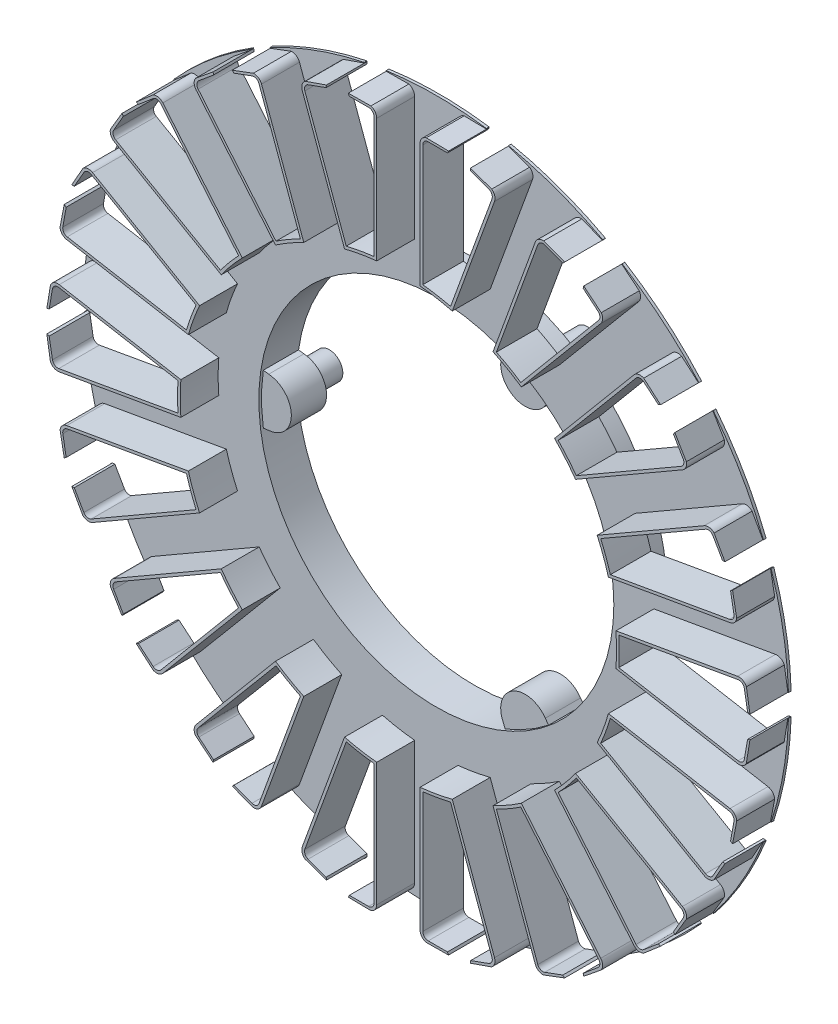
SolidWorks part; units mm, degrees
ref_plane "Front Plane" through (0, 0, 0) normal (0, 0, 1) x (1, 0, 0)
ref_plane "Top Plane" through (0, 0, 0) normal (0, 1, 0) x (1, 0, 0)
ref_plane "Right Plane" through (0, 0, 0) normal (1, 0, 0) x (0, 0, -1)
sketch "Sketch1" plane through (0, 0, 0) normal (0, 0, 1) x (1, 0, 0)
  line L0 (0, 0) -> (0, 65) construction
  line L1 (4.5, 40.5008) -> (4.5, 64.844) construction
  line L2 (-4.5, 40.5008) -> (-4.5, 62.8398)
  line L3 (9.25, 64.2333) -> (9.25, 64.3385)
  line L4 (9.05, 63.8336) -> (9.25, 64.2333)
  line L5 (-5.5018, 63.8398) -> (-9.05, 63.8336)
  line L6 (-9.25, 64.2333) -> (-9.25, 64.3385)
  line L7 (5.5018, 63.8398) -> (9.05, 63.8336)
  line L8 (-4.5, 0) -> (-4.5, 65) construction
  line L9 (-9.05, 63.8336) -> (-9.25, 64.2333)
  line L10 (4.5, 62.8398) -> (4.5, 40.5008)
  line L11 (4.5, 0) -> (4.5, 65) construction
  line L12 (25.7211, 57.5111) -> (18.0807, 36.5192)
  line L13 (13.3282, 63.0793) -> (13.2769, 63.5232)
  line L14 (13.2769, 63.5232) -> (13.3129, 63.6221)
  line L15 (16.6646, 61.8715) -> (13.3282, 63.0793)
  line L16 (27.0045, 58.1081) -> (30.3366, 56.8887)
  line L17 (30.6612, 57.1959) -> (30.6972, 57.2947)
  line L18 (30.3366, 56.8887) -> (30.6612, 57.1959)
  line L19 (9.6235, 39.5974) -> (17.2639, 60.5892)
  line L20 (43.8399, 45.2456) -> (29.4806, 28.1328)
  line L21 (34.0988, 54.7166) -> (34.2024, 55.1513)
  line L22 (34.2024, 55.1513) -> (34.2701, 55.2319)
  line L23 (36.8209, 52.4406) -> (34.0988, 54.7166)
  line L24 (45.25, 45.3677) -> (47.9642, 43.0822)
  line L25 (48.3743, 43.2598) -> (48.4419, 43.3403)
  line L26 (47.9642, 43.0822) -> (48.3743, 43.2598)
  line L27 (22.5862, 33.9179) -> (36.9455, 51.0307)
  line L28 (56.6709, 27.5228) -> (37.3247, 16.3533)
  line L29 (50.7565, 39.7543) -> (51.0027, 40.1274)
  line L30 (51.0027, 40.1274) -> (51.0937, 40.18)
  line L31 (52.5361, 36.6846) -> (50.7565, 39.7543)
  line L32 (58.0378, 27.1553) -> (59.8065, 24.0793)
  line L33 (60.2527, 24.1059) -> (60.3437, 24.1585)
  line L34 (59.8065, 24.0793) -> (60.2527, 24.1059)
  line L35 (32.8247, 24.1475) -> (52.1709, 35.317)
  line L36 (62.6666, 6.4804) -> (40.6669, 2.6013)
  line L37 (61.2923, 19.9971) -> (61.6512, 20.2635)
  line L38 (61.6512, 20.2635) -> (61.7548, 20.2817)
  line L39 (61.9146, 16.5038) -> (61.2923, 19.9971)
  line L40 (63.8253, 5.6675) -> (64.4354, 2.1721)
  line L41 (64.8637, 2.0445) -> (64.9673, 2.0628)
  line L42 (64.4354, 2.1721) -> (64.8637, 2.0445)
  line L43 (39.1041, 11.4645) -> (61.1038, 15.3437)
  line L44 (61.1038, -15.3437) -> (39.1041, -11.4645)
  line L45 (64.4354, -2.1721) -> (64.8637, -2.0445)
  line L46 (64.8637, -2.0445) -> (64.9673, -2.0628)
  line L47 (63.8253, -5.6675) -> (64.4354, -2.1721)
  line L48 (61.9146, -16.5038) -> (61.2923, -19.9971)
  line L49 (61.6512, -20.2635) -> (61.7548, -20.2817)
  line L50 (61.2923, -19.9971) -> (61.6512, -20.2635)
  line L51 (40.6669, -2.6013) -> (62.6666, -6.4804)
  line L52 (52.1709, -35.317) -> (32.8247, -24.1475)
  line L53 (59.8065, -24.0793) -> (60.2527, -24.1059)
  line L54 (60.2527, -24.1059) -> (60.3437, -24.1585)
  line L55 (58.0378, -27.1553) -> (59.8065, -24.0793)
  line L56 (52.5361, -36.6846) -> (50.7565, -39.7543)
  line L57 (51.0027, -40.1274) -> (51.0937, -40.18)
  line L58 (50.7565, -39.7543) -> (51.0027, -40.1274)
  line L59 (37.3247, -16.3533) -> (56.6709, -27.5228)
  line L60 (36.9455, -51.0307) -> (22.5862, -33.9179)
  line L61 (47.9642, -43.0822) -> (48.3743, -43.2598)
  line L62 (48.3743, -43.2598) -> (48.4419, -43.3403)
  line L63 (45.25, -45.3677) -> (47.9642, -43.0822)
  line L64 (36.8209, -52.4406) -> (34.0988, -54.7166)
  line L65 (34.2024, -55.1513) -> (34.2701, -55.2319)
  line L66 (34.0988, -54.7166) -> (34.2024, -55.1513)
  line L67 (29.4806, -28.1328) -> (43.8399, -45.2456)
  line L68 (17.2639, -60.5892) -> (9.6235, -39.5974)
  line L69 (30.3366, -56.8887) -> (30.6612, -57.1959)
  line L70 (30.6612, -57.1959) -> (30.6972, -57.2947)
  line L71 (27.0045, -58.1081) -> (30.3366, -56.8887)
  line L72 (16.6646, -61.8715) -> (13.3282, -63.0793)
  line L73 (13.2769, -63.5232) -> (13.3129, -63.6221)
  line L74 (13.3282, -63.0793) -> (13.2769, -63.5232)
  line L75 (18.0807, -36.5192) -> (25.7211, -57.5111)
  line L76 (-4.5, -62.8398) -> (-4.5, -40.5008)
  line L77 (9.05, -63.8336) -> (9.25, -64.2333)
  line L78 (9.25, -64.2333) -> (9.25, -64.3385)
  line L79 (5.5018, -63.8398) -> (9.05, -63.8336)
  line L80 (-5.5018, -63.8398) -> (-9.05, -63.8336)
  line L81 (-9.25, -64.2333) -> (-9.25, -64.3385)
  line L82 (-9.05, -63.8336) -> (-9.25, -64.2333)
  line L83 (4.5, -40.5008) -> (4.5, -62.8398)
  line L84 (-25.7211, -57.5111) -> (-18.0807, -36.5192)
  line L85 (-13.3282, -63.0793) -> (-13.2769, -63.5232)
  line L86 (-13.2769, -63.5232) -> (-13.3129, -63.6221)
  line L87 (-16.6646, -61.8715) -> (-13.3282, -63.0793)
  line L88 (-27.0045, -58.1081) -> (-30.3366, -56.8887)
  line L89 (-30.6612, -57.1959) -> (-30.6972, -57.2947)
  line L90 (-30.3366, -56.8887) -> (-30.6612, -57.1959)
  line L91 (-9.6235, -39.5974) -> (-17.2639, -60.5892)
  line L92 (-43.8399, -45.2456) -> (-29.4806, -28.1328)
  line L93 (-34.0988, -54.7166) -> (-34.2024, -55.1513)
  line L94 (-34.2024, -55.1513) -> (-34.2701, -55.2319)
  line L95 (-36.8209, -52.4406) -> (-34.0988, -54.7166)
  line L96 (-45.25, -45.3677) -> (-47.9642, -43.0822)
  line L97 (-48.3743, -43.2598) -> (-48.4419, -43.3403)
  line L98 (-47.9642, -43.0822) -> (-48.3743, -43.2598)
  line L99 (-22.5862, -33.9179) -> (-36.9455, -51.0307)
  line L100 (-56.6709, -27.5228) -> (-37.3247, -16.3533)
  line L101 (-50.7565, -39.7543) -> (-51.0027, -40.1274)
  line L102 (-51.0027, -40.1274) -> (-51.0937, -40.18)
  line L103 (-52.5361, -36.6846) -> (-50.7565, -39.7543)
  line L104 (-58.0378, -27.1553) -> (-59.8065, -24.0793)
  line L105 (-60.2527, -24.1059) -> (-60.3437, -24.1585)
  line L106 (-59.8065, -24.0793) -> (-60.2527, -24.1059)
  line L107 (-32.8247, -24.1475) -> (-52.1709, -35.317)
  line L108 (-62.6666, -6.4804) -> (-40.6669, -2.6013)
  line L109 (-61.2923, -19.9971) -> (-61.6512, -20.2635)
  line L110 (-61.6512, -20.2635) -> (-61.7548, -20.2817)
  line L111 (-61.9146, -16.5038) -> (-61.2923, -19.9971)
  line L112 (-63.8253, -5.6675) -> (-64.4354, -2.1721)
  line L113 (-64.8637, -2.0445) -> (-64.9673, -2.0628)
  line L114 (-64.4354, -2.1721) -> (-64.8637, -2.0445)
  line L115 (-39.1041, -11.4645) -> (-61.1038, -15.3437)
  line L116 (-61.1038, 15.3437) -> (-39.1041, 11.4645)
  line L117 (-64.4354, 2.1721) -> (-64.8637, 2.0445)
  line L118 (-64.8637, 2.0445) -> (-64.9673, 2.0628)
  line L119 (-63.8253, 5.6675) -> (-64.4354, 2.1721)
  line L120 (-61.9146, 16.5038) -> (-61.2923, 19.9971)
  line L121 (-61.6512, 20.2635) -> (-61.7548, 20.2817)
  line L122 (-61.2923, 19.9971) -> (-61.6512, 20.2635)
  line L123 (-40.6669, 2.6013) -> (-62.6666, 6.4804)
  line L124 (-52.1709, 35.317) -> (-32.8247, 24.1475)
  line L125 (-59.8065, 24.0793) -> (-60.2527, 24.1059)
  line L126 (-60.2527, 24.1059) -> (-60.3437, 24.1585)
  line L127 (-58.0378, 27.1553) -> (-59.8065, 24.0793)
  line L128 (-52.5361, 36.6846) -> (-50.7565, 39.7543)
  line L129 (-51.0027, 40.1274) -> (-51.0937, 40.18)
  line L130 (-50.7565, 39.7543) -> (-51.0027, 40.1274)
  line L131 (-37.3247, 16.3533) -> (-56.6709, 27.5228)
  line L132 (-36.9455, 51.0307) -> (-22.5862, 33.9179)
  line L133 (-47.9642, 43.0822) -> (-48.3743, 43.2598)
  line L134 (-48.3743, 43.2598) -> (-48.4419, 43.3403)
  line L135 (-45.25, 45.3677) -> (-47.9642, 43.0822)
  line L136 (-36.8209, 52.4406) -> (-34.0988, 54.7166)
  line L137 (-34.2024, 55.1513) -> (-34.2701, 55.2319)
  line L138 (-34.0988, 54.7166) -> (-34.2024, 55.1513)
  line L139 (-29.4806, 28.1328) -> (-43.8399, 45.2456)
  line L140 (-17.2639, 60.5892) -> (-9.6235, 39.5974)
  line L141 (-30.3366, 56.8887) -> (-30.6612, 57.1959)
  line L142 (-30.6612, 57.1959) -> (-30.6972, 57.2947)
  line L143 (-27.0045, 58.1081) -> (-30.3366, 56.8887)
  line L144 (-16.6646, 61.8715) -> (-13.3282, 63.0793)
  line L145 (-13.2769, 63.5232) -> (-13.3129, 63.6221)
  line L146 (-13.3282, 63.0793) -> (-13.2769, 63.5232)
  line L147 (-18.0807, 36.5192) -> (-25.7211, 57.5111)
  circle A0 centre (0, 0) radius 32.75
  arc A1 (-4.5, 40.5008) -> (-9.6235, 39.5974) centre (0, 0) ccw
  arc A3 (9.25, 64.3385) -> (-9.25, 64.3385) centre (0, 0) ccw
  arc A6 (-5.5018, 63.8398) -> (-4.5, 62.8398) centre (-5.5, 62.8398) cw
  arc A7 (5.5018, 63.8398) -> (4.5, 62.8398) centre (5.5, 62.8398) ccw
  arc A8 (30.6972, 57.2947) -> (13.3129, 63.6221) centre (0, 0) ccw
  arc A9 (16.6646, 61.8715) -> (17.2639, 60.5892) centre (16.3242, 60.9313) cw
  arc A10 (27.0045, 58.1081) -> (25.7211, 57.5111) centre (26.6608, 57.169) ccw
  arc A11 (48.4419, 43.3403) -> (34.2701, 55.2319) centre (0, 0) ccw
  arc A12 (36.8209, 52.4406) -> (36.9455, 51.0307) centre (36.1794, 51.6734) cw
  arc A13 (45.25, 45.3677) -> (43.8399, 45.2456) centre (44.6059, 44.6028) ccw
  arc A14 (60.3437, 24.1585) -> (51.0937, 40.18) centre (0, 0) ccw
  arc A15 (52.5361, 36.6846) -> (52.1709, 35.317) centre (51.6709, 36.1831) cw
  arc A16 (58.0378, 27.1553) -> (56.6709, 27.5228) centre (57.1709, 26.6568) ccw
  arc A17 (64.9673, 2.0628) -> (61.7548, 20.2817) centre (0, 0) ccw
  arc A18 (61.9146, 16.5038) -> (61.1038, 15.3437) centre (60.9301, 16.3285) cw
  arc A19 (63.8253, 5.6675) -> (62.6666, 6.4804) centre (62.8402, 5.4956) ccw
  arc A20 (61.7548, -20.2817) -> (64.9673, -2.0628) centre (0, 0) ccw
  arc A21 (63.8253, -5.6675) -> (62.6666, -6.4804) centre (62.8402, -5.4956) cw
  arc A22 (61.9146, -16.5038) -> (61.1038, -15.3437) centre (60.9301, -16.3285) ccw
  arc A23 (51.0937, -40.18) -> (60.3437, -24.1585) centre (0, 0) ccw
  arc A24 (58.0378, -27.1553) -> (56.6709, -27.5228) centre (57.1709, -26.6568) cw
  arc A25 (52.5361, -36.6846) -> (52.1709, -35.317) centre (51.6709, -36.1831) ccw
  arc A26 (34.2701, -55.2319) -> (48.4419, -43.3403) centre (0, 0) ccw
  arc A27 (45.25, -45.3677) -> (43.8399, -45.2456) centre (44.6059, -44.6028) cw
  arc A28 (36.8209, -52.4406) -> (36.9455, -51.0307) centre (36.1794, -51.6734) ccw
  arc A29 (13.3129, -63.6221) -> (30.6972, -57.2947) centre (0, 0) ccw
  arc A30 (27.0045, -58.1081) -> (25.7211, -57.5111) centre (26.6608, -57.169) cw
  arc A31 (16.6646, -61.8715) -> (17.2639, -60.5892) centre (16.3242, -60.9313) ccw
  arc A32 (-9.25, -64.3385) -> (9.25, -64.3385) centre (0, 0) ccw
  arc A33 (5.5018, -63.8398) -> (4.5, -62.8398) centre (5.5, -62.8398) cw
  arc A34 (-5.5018, -63.8398) -> (-4.5, -62.8398) centre (-5.5, -62.8398) ccw
  arc A35 (-30.6972, -57.2947) -> (-13.3129, -63.6221) centre (0, 0) ccw
  arc A36 (-16.6646, -61.8715) -> (-17.2639, -60.5892) centre (-16.3242, -60.9313) cw
  arc A37 (-27.0045, -58.1081) -> (-25.7211, -57.5111) centre (-26.6608, -57.169) ccw
  arc A38 (-48.4419, -43.3403) -> (-34.2701, -55.2319) centre (0, 0) ccw
  arc A39 (-36.8209, -52.4406) -> (-36.9455, -51.0307) centre (-36.1794, -51.6734) cw
  arc A40 (-45.25, -45.3677) -> (-43.8399, -45.2456) centre (-44.6059, -44.6028) ccw
  arc A41 (-60.3437, -24.1585) -> (-51.0937, -40.18) centre (0, 0) ccw
  arc A42 (-52.5361, -36.6846) -> (-52.1709, -35.317) centre (-51.6709, -36.1831) cw
  arc A43 (-58.0378, -27.1553) -> (-56.6709, -27.5228) centre (-57.1709, -26.6568) ccw
  arc A44 (-64.9673, -2.0628) -> (-61.7548, -20.2817) centre (0, 0) ccw
  arc A45 (-61.9146, -16.5038) -> (-61.1038, -15.3437) centre (-60.9301, -16.3285) cw
  arc A46 (-63.8253, -5.6675) -> (-62.6666, -6.4804) centre (-62.8402, -5.4956) ccw
  arc A47 (-61.7548, 20.2817) -> (-64.9673, 2.0628) centre (0, 0) ccw
  arc A48 (-63.8253, 5.6675) -> (-62.6666, 6.4804) centre (-62.8402, 5.4956) cw
  arc A49 (-61.9146, 16.5038) -> (-61.1038, 15.3437) centre (-60.9301, 16.3285) ccw
  arc A50 (-51.0937, 40.18) -> (-60.3437, 24.1585) centre (0, 0) ccw
  arc A51 (-58.0378, 27.1553) -> (-56.6709, 27.5228) centre (-57.1709, 26.6568) cw
  arc A52 (-52.5361, 36.6846) -> (-52.1709, 35.317) centre (-51.6709, 36.1831) ccw
  arc A53 (-34.2701, 55.2319) -> (-48.4419, 43.3403) centre (0, 0) ccw
  arc A54 (-45.25, 45.3677) -> (-43.8399, 45.2456) centre (-44.6059, 44.6028) cw
  arc A55 (-36.8209, 52.4406) -> (-36.9455, 51.0307) centre (-36.1794, 51.6734) ccw
  arc A56 (-13.3129, 63.6221) -> (-30.6972, 57.2947) centre (0, 0) ccw
  arc A57 (-27.0045, 58.1081) -> (-25.7211, 57.5111) centre (-26.6608, 57.169) cw
  arc A58 (-16.6646, 61.8715) -> (-17.2639, 60.5892) centre (-16.3242, 60.9313) ccw
  arc A59 (-18.0807, 36.5192) -> (-22.5862, 33.9179) centre (0, 0) ccw
  arc A60 (-29.4806, 28.1328) -> (-32.8247, 24.1475) centre (0, 0) ccw
  arc A61 (-37.3247, 16.3533) -> (-39.1041, 11.4645) centre (0, 0) ccw
  arc A62 (-40.6669, 2.6013) -> (-40.6669, -2.6013) centre (0, 0) ccw
  arc A63 (-39.1041, -11.4645) -> (-37.3247, -16.3533) centre (0, 0) ccw
  arc A64 (-32.8247, -24.1475) -> (-29.4806, -28.1328) centre (0, 0) ccw
  arc A65 (-22.5862, -33.9179) -> (-18.0807, -36.5192) centre (0, 0) ccw
  arc A66 (-9.6235, -39.5974) -> (-4.5, -40.5008) centre (0, 0) ccw
  arc A67 (4.5, -40.5008) -> (9.6235, -39.5974) centre (0, 0) ccw
  arc A68 (18.0807, -36.5192) -> (22.5862, -33.9179) centre (0, 0) ccw
  arc A69 (29.4806, -28.1328) -> (32.8247, -24.1475) centre (0, 0) ccw
  arc A70 (37.3247, -16.3533) -> (39.1041, -11.4645) centre (0, 0) ccw
  arc A71 (40.6669, -2.6013) -> (40.6669, 2.6013) centre (0, 0) ccw
  arc A72 (39.1041, 11.4645) -> (37.3247, 16.3533) centre (0, 0) ccw
  arc A73 (32.8247, 24.1475) -> (29.4806, 28.1328) centre (0, 0) ccw
  arc A74 (22.5862, 33.9179) -> (18.0807, 36.5192) centre (0, 0) ccw
  arc A75 (9.6235, 39.5974) -> (4.5, 40.5008) centre (0, 0) ccw
  point P12 (9.25, 0)
  point P13 (9.25, 65)
  point P14 (-9.25, 0)
  point P15 (-9.25, 65)
  point P17 (-9.25, 63.8333)
  point P18 (-9.25, 0)
  point P21 (-9.25, 65)
  point P270 (0, 0)
  dimension "D1" = 65.5
  dimension "D2" = 8
  dimension "D3" = 130
  dimension "D4" = 18
  dimension "D10" = 1
  dimension "D11" = 0.4
  dimension "D12" = 0.2
  dimension "D6" = 4.5
  dimension "D7" = 4.5
extrude "Boss-Extrude2" add sketch "Sketch1" along normal blind 0.5
sketch "Sketch3" plane through (0, 0, 0.5) normal (0, 0, 1) x (1, 0, 0)
  line L0 (-32.8247, 24.1475) -> (-52.1709, 35.317) construction
  line L1 (-56.6709, 27.5228) -> (-37.3247, 16.3533) construction
  line L2 (-53.1303, 36.5298) -> (-51.0027, 40.1274)
  line L3 (-60.2527, 24.1059) -> (-59.8065, 24.0793) construction
  line L4 (-50.7565, 39.7543) -> (-52.5361, 36.6846)
  line L5 (-50.7565, 39.7543) -> (-51.0027, 40.1274) construction
  line L6 (-51.0027, 40.1274) -> (-51.0937, 40.18) construction
  line L7 (-52.5361, 36.6846) -> (-50.7565, 39.7543) construction
  line L8 (-52.5361, 36.6846) -> (-50.7565, 39.7543)
  line L9 (-51.0027, 40.1274) -> (-51.0937, 40.18)
  line L10 (-50.7565, 39.7543) -> (-51.0027, 40.1274)
  line L11 (-60.2527, 24.1059) -> (-59.8065, 24.0793)
  line L12 (0, 0) -> (-56.2917, 32.5) construction
  line L13 (-32.8247, 24.1475) -> (-52.1709, 35.317)
  line L14 (-56.6709, 27.5228) -> (-37.3247, 16.3533)
  line L15 (-58.2009, 27.7473) -> (-60.2527, 24.1059)
  line L16 (-37.1201, 16.8125) -> (-37.0747, 16.7863)
  line L17 (-60.2229, 24.605) -> (-60.0857, 24.5968)
  line L18 (-59.8065, 24.0793) -> (-58.0378, 27.1553)
  line L19 (-33.0747, 23.7145) -> (-33.1201, 23.7407)
  line L20 (-53.113, 36.5959) -> (-53.113, 36.5959)
  line L21 (-53.113, 36.5959) -> (-53.113, 36.5959)
  line L22 (-53.113, 36.5959) -> (-53.113, 36.5959)
  line L23 (-60.0857, 24.5968) -> (-58.4713, 27.4045) construction
  line L24 (-59.8065, 24.0793) -> (-58.0378, 27.1553) construction
  line L25 (-32.685, 23.4895) -> (-52.4209, 34.884)
  line L26 (-36.685, 16.5613) -> (-56.4209, 27.9558)
  line L27 (-54.185, 35.9025) -> (-54.2917, 35.9641)
  line L28 (-33.0747, 23.7145) -> (-52.4209, 34.884) construction
  line L29 (-56.4209, 27.9558) -> (-37.0747, 16.7863) construction
  line L30 (2, 3.4641) -> (-54.2917, 35.9641) construction
  line L31 (-2, -3.4641) -> (-58.2917, 29.0359) construction
  line L32 (-58.185, 28.9743) -> (-58.2917, 29.0359)
  line L33 (-22.6799, 33.2518) -> (-37.3285, 50.7093)
  line L34 (-22.5862, 33.9179) -> (-36.9455, 51.0307)
  line L35 (-37.3933, 52.5546) -> (-34.2024, 55.1513)
  line L36 (-34.0988, 54.7166) -> (-34.2024, 55.1513)
  line L37 (-34.0988, 54.7166) -> (-36.8209, 52.4406)
  line L38 (-45.2008, 45.9798) -> (-48.3743, 43.2598)
  line L39 (-48.3743, 43.2598) -> (-47.9642, 43.0822)
  line L40 (-47.9642, 43.0822) -> (-45.25, 45.3677)
  line L41 (-28.8083, 28.1095) -> (-43.4569, 45.567)
  line L42 (-43.8399, 45.2456) -> (-29.4806, 28.1328)
  line L43 (-9.9394, 39.0035) -> (-17.7337, 60.4182)
  line L44 (-9.6235, 39.5974) -> (-17.2639, 60.5892)
  line L45 (-17.1635, 62.1745) -> (-13.2769, 63.5232)
  line L46 (-13.3282, 63.0793) -> (-13.2769, 63.5232)
  line L47 (-13.3282, 63.0793) -> (-16.6646, 61.8715)
  line L48 (-26.7489, 58.6664) -> (-30.6612, 57.1959)
  line L49 (-30.6612, 57.1959) -> (-30.3366, 56.8887)
  line L50 (-30.3366, 56.8887) -> (-27.0045, 58.1081)
  line L51 (-17.4569, 36.2673) -> (-25.2513, 57.6821)
  line L52 (-25.7211, 57.5111) -> (-18.0807, 36.5192)
  line L53 (4, 40.0507) -> (4, 62.8398)
  line L54 (4.5, 40.5008) -> (4.5, 62.8398)
  line L55 (5.1365, 64.2951) -> (9.25, 64.2333)
  line L56 (9.05, 63.8336) -> (9.25, 64.2333)
  line L57 (9.05, 63.8336) -> (5.5018, 63.8398)
  line L58 (-5.0706, 64.2771) -> (-9.25, 64.2333)
  line L59 (-9.25, 64.2333) -> (-9.05, 63.8336)
  line L60 (-9.05, 63.8336) -> (-5.5018, 63.8398)
  line L61 (-4, 40.0507) -> (-4, 62.8398)
  line L62 (-4.5, 62.8398) -> (-4.5, 40.5008)
  line L63 (17.4569, 36.2673) -> (25.2513, 57.6821)
  line L64 (18.0807, 36.5192) -> (25.7211, 57.5111)
  line L65 (26.817, 58.6609) -> (30.6612, 57.1959)
  line L66 (30.3366, 56.8887) -> (30.6612, 57.1959)
  line L67 (30.3366, 56.8887) -> (27.0045, 58.1081)
  line L68 (17.2192, 62.1349) -> (13.2769, 63.5232)
  line L69 (13.2769, 63.5232) -> (13.3282, 63.0793)
  line L70 (13.3282, 63.0793) -> (16.6646, 61.8715)
  line L71 (9.9394, 39.0035) -> (17.7337, 60.4182)
  line L72 (17.2639, 60.5892) -> (9.6235, 39.5974)
  line L73 (28.8083, 28.1095) -> (43.4569, 45.567)
  line L74 (29.4806, 28.1328) -> (43.8399, 45.2456)
  line L75 (45.2629, 45.9512) -> (48.3743, 43.2598)
  line L76 (47.9642, 43.0822) -> (48.3743, 43.2598)
  line L77 (47.9642, 43.0822) -> (45.25, 45.3677)
  line L78 (37.4322, 52.4984) -> (34.2024, 55.1513)
  line L79 (34.2024, 55.1513) -> (34.0988, 54.7166)
  line L80 (34.0988, 54.7166) -> (36.8209, 52.4406)
  line L81 (22.6799, 33.2518) -> (37.3285, 50.7093)
  line L82 (36.9455, 51.0307) -> (22.5862, 33.9179)
  line L83 (36.685, 16.5613) -> (56.4209, 27.9558)
  line L84 (37.3247, 16.3533) -> (56.6709, 27.5228)
  line L85 (58.2495, 27.6992) -> (60.2527, 24.1059)
  line L86 (59.8065, 24.0793) -> (60.2527, 24.1059)
  line L87 (59.8065, 24.0793) -> (58.0378, 27.1553)
  line L88 (53.1303, 36.5298) -> (51.0027, 40.1274)
  line L89 (51.0027, 40.1274) -> (50.7565, 39.7543)
  line L90 (50.7565, 39.7543) -> (52.5361, 36.6846)
  line L91 (32.685, 23.4895) -> (52.4209, 34.884)
  line L92 (52.1709, 35.317) -> (32.8247, 24.1475)
  line L93 (40.1369, 3.0155) -> (62.5798, 6.9728)
  line L94 (40.6669, 2.6013) -> (62.6666, 6.4804)
  line L95 (64.2103, 6.1062) -> (64.8637, 2.0445)
  line L96 (64.4354, 2.1721) -> (64.8637, 2.0445)
  line L97 (64.4354, 2.1721) -> (63.8253, 5.6675)
  line L98 (62.4201, 16.1552) -> (61.6512, 20.2635)
  line L99 (61.6512, 20.2635) -> (61.2923, 19.9971)
  line L100 (61.2923, 19.9971) -> (61.9146, 16.5038)
  line L101 (38.7477, 10.894) -> (61.1906, 14.8513)
  line L102 (61.1038, 15.3437) -> (39.1041, 11.4645)
  line L103 (38.7477, -10.894) -> (61.1906, -14.8513)
  line L104 (39.1041, -11.4645) -> (61.1038, -15.3437)
  line L105 (62.4264, -16.2232) -> (61.6512, -20.2635)
  line L106 (61.2923, -19.9971) -> (61.6512, -20.2635)
  line L107 (61.2923, -19.9971) -> (61.9146, -16.5038)
  line L108 (64.1811, -6.168) -> (64.8637, -2.0445)
  line L109 (64.8637, -2.0445) -> (64.4354, -2.1721)
  line L110 (64.4354, -2.1721) -> (63.8253, -5.6675)
  line L111 (40.1369, -3.0155) -> (62.5798, -6.9728)
  line L112 (62.6666, -6.4804) -> (40.6669, -2.6013)
  line L113 (32.685, -23.4895) -> (52.4209, -34.884)
  line L114 (32.8247, -24.1475) -> (52.1709, -35.317)
  line L115 (53.113, -36.5959) -> (51.0027, -40.1274)
  line L116 (50.7565, -39.7543) -> (51.0027, -40.1274)
  line L117 (50.7565, -39.7543) -> (52.5361, -36.6846)
  line L118 (58.2009, -27.7473) -> (60.2527, -24.1059)
  line L119 (60.2527, -24.1059) -> (59.8065, -24.0793)
  line L120 (59.8065, -24.0793) -> (58.0378, -27.1553)
  line L121 (36.685, -16.5613) -> (56.4209, -27.9558)
  line L122 (56.6709, -27.5228) -> (37.3247, -16.3533)
  line L123 (22.6799, -33.2518) -> (37.3285, -50.7093)
  line L124 (22.5862, -33.9179) -> (36.9455, -51.0307)
  line L125 (37.3933, -52.5546) -> (34.2024, -55.1513)
  line L126 (34.0988, -54.7166) -> (34.2024, -55.1513)
  line L127 (34.0988, -54.7166) -> (36.8209, -52.4406)
  line L128 (45.2008, -45.9798) -> (48.3743, -43.2598)
  line L129 (48.3743, -43.2598) -> (47.9642, -43.0822)
  line L130 (47.9642, -43.0822) -> (45.25, -45.3677)
  line L131 (28.8083, -28.1095) -> (43.4569, -45.567)
  line L132 (43.8399, -45.2456) -> (29.4806, -28.1328)
  line L133 (9.9394, -39.0035) -> (17.7337, -60.4182)
  line L134 (9.6235, -39.5974) -> (17.2639, -60.5892)
  line L135 (17.1635, -62.1745) -> (13.2769, -63.5232)
  line L136 (13.3282, -63.0793) -> (13.2769, -63.5232)
  line L137 (13.3282, -63.0793) -> (16.6646, -61.8715)
  line L138 (26.7489, -58.6664) -> (30.6612, -57.1959)
  line L139 (30.6612, -57.1959) -> (30.3366, -56.8887)
  line L140 (30.3366, -56.8887) -> (27.0045, -58.1081)
  line L141 (17.4569, -36.2673) -> (25.2513, -57.6821)
  line L142 (25.7211, -57.5111) -> (18.0807, -36.5192)
  line L143 (-4, -40.0507) -> (-4, -62.8398)
  line L144 (-4.5, -40.5008) -> (-4.5, -62.8398)
  line L145 (-5.1365, -64.2951) -> (-9.25, -64.2333)
  line L146 (-9.05, -63.8336) -> (-9.25, -64.2333)
  line L147 (-9.05, -63.8336) -> (-5.5018, -63.8398)
  line L148 (5.0706, -64.2771) -> (9.25, -64.2333)
  line L149 (9.25, -64.2333) -> (9.05, -63.8336)
  line L150 (9.05, -63.8336) -> (5.5018, -63.8398)
  line L151 (4, -40.0507) -> (4, -62.8398)
  line L152 (4.5, -62.8398) -> (4.5, -40.5008)
  line L153 (-17.4569, -36.2673) -> (-25.2513, -57.6821)
  line L154 (-18.0807, -36.5192) -> (-25.7211, -57.5111)
  line L155 (-26.817, -58.6609) -> (-30.6612, -57.1959)
  line L156 (-30.3366, -56.8887) -> (-30.6612, -57.1959)
  line L157 (-30.3366, -56.8887) -> (-27.0045, -58.1081)
  line L158 (-17.2192, -62.1349) -> (-13.2769, -63.5232)
  line L159 (-13.2769, -63.5232) -> (-13.3282, -63.0793)
  line L160 (-13.3282, -63.0793) -> (-16.6646, -61.8715)
  line L161 (-9.9394, -39.0035) -> (-17.7337, -60.4182)
  line L162 (-17.2639, -60.5892) -> (-9.6235, -39.5974)
  line L163 (-28.8083, -28.1095) -> (-43.4569, -45.567)
  line L164 (-29.4806, -28.1328) -> (-43.8399, -45.2456)
  line L165 (-45.2629, -45.9512) -> (-48.3743, -43.2598)
  line L166 (-47.9642, -43.0822) -> (-48.3743, -43.2598)
  line L167 (-47.9642, -43.0822) -> (-45.25, -45.3677)
  line L168 (-37.4322, -52.4984) -> (-34.2024, -55.1513)
  line L169 (-34.2024, -55.1513) -> (-34.0988, -54.7166)
  line L170 (-34.0988, -54.7166) -> (-36.8209, -52.4406)
  line L171 (-22.6799, -33.2518) -> (-37.3285, -50.7093)
  line L172 (-36.9455, -51.0307) -> (-22.5862, -33.9179)
  line L173 (-36.685, -16.5613) -> (-56.4209, -27.9558)
  line L174 (-37.3247, -16.3533) -> (-56.6709, -27.5228)
  line L175 (-58.2495, -27.6992) -> (-60.2527, -24.1059)
  line L176 (-59.8065, -24.0793) -> (-60.2527, -24.1059)
  line L177 (-59.8065, -24.0793) -> (-58.0378, -27.1553)
  line L178 (-53.1303, -36.5298) -> (-51.0027, -40.1274)
  line L179 (-51.0027, -40.1274) -> (-50.7565, -39.7543)
  line L180 (-50.7565, -39.7543) -> (-52.5361, -36.6846)
  line L181 (-32.685, -23.4895) -> (-52.4209, -34.884)
  line L182 (-52.1709, -35.317) -> (-32.8247, -24.1475)
  line L183 (-40.1369, -3.0155) -> (-62.5798, -6.9728)
  line L184 (-40.6669, -2.6013) -> (-62.6666, -6.4804)
  line L185 (-64.2103, -6.1062) -> (-64.8637, -2.0445)
  line L186 (-64.4354, -2.1721) -> (-64.8637, -2.0445)
  line L187 (-64.4354, -2.1721) -> (-63.8253, -5.6675)
  line L188 (-62.4201, -16.1552) -> (-61.6512, -20.2635)
  line L189 (-61.6512, -20.2635) -> (-61.2923, -19.9971)
  line L190 (-61.2923, -19.9971) -> (-61.9146, -16.5038)
  line L191 (-38.7477, -10.894) -> (-61.1906, -14.8513)
  line L192 (-61.1038, -15.3437) -> (-39.1041, -11.4645)
  line L193 (-38.7477, 10.894) -> (-61.1906, 14.8513)
  line L194 (-39.1041, 11.4645) -> (-61.1038, 15.3437)
  line L195 (-62.4264, 16.2232) -> (-61.6512, 20.2635)
  line L196 (-61.2923, 19.9971) -> (-61.6512, 20.2635)
  line L197 (-61.2923, 19.9971) -> (-61.9146, 16.5038)
  line L198 (-64.1811, 6.168) -> (-64.8637, 2.0445)
  line L199 (-64.8637, 2.0445) -> (-64.4354, 2.1721)
  line L200 (-64.4354, 2.1721) -> (-63.8253, 5.6675)
  line L201 (-40.1369, 3.0155) -> (-62.5798, 6.9728)
  line L202 (-62.6666, 6.4804) -> (-40.6669, 2.6013)
  arc A0 (-36.685, 16.5613) -> (-38.7477, 10.894) centre (0, 0) ccw
  arc A1 (-37.3247, 16.3533) -> (-39.1041, 11.4645) centre (0, 0) ccw
  arc A2 (-56.6709, 27.5228) -> (-58.0378, 27.1553) centre (-57.1709, 26.6568) ccw construction
  arc A3 (-51.0937, 40.18) -> (-60.3437, 24.1585) centre (0, 0) ccw construction
  arc A4 (-52.5361, 36.6846) -> (-52.1709, 35.317) centre (-51.6709, 36.1831) ccw construction
  arc A5 (-52.5361, 36.6846) -> (-52.1709, 35.317) centre (-51.6709, 36.1831) ccw
  arc A6 (-51.0937, 40.18) -> (-60.3437, 24.1585) centre (0, 0) ccw construction
  arc A7 (-56.6709, 27.5228) -> (-58.0378, 27.1553) centre (-57.1709, 26.6568) ccw
  arc A8 (-53.113, 36.5959) -> (-52.4209, 34.884) centre (-51.6709, 36.1831) ccw
  arc A9 (-56.4209, 27.9558) -> (-58.2009, 27.7473) centre (-57.1709, 26.6568) ccw
  arc A10 (-53.113, 36.5959) -> (-59.8796, 23.9727) centre (0, 0) ccw construction
  arc A11 (-36.8209, 52.4406) -> (-36.9455, 51.0307) centre (-36.1794, 51.6734) ccw
  arc A12 (-37.3933, 52.5546) -> (-37.3285, 50.7093) centre (-36.1794, 51.6734) ccw
  arc A13 (-56.4209, 27.9558) -> (-58.4713, 27.4045) centre (-57.1709, 26.6568) ccw construction
  arc A14 (-43.8399, 45.2456) -> (-45.25, 45.3677) centre (-44.6059, 44.6028) ccw
  arc A15 (-43.4569, 45.567) -> (-45.2008, 45.9798) centre (-44.6059, 44.6028) ccw
  arc A16 (-16.6646, 61.8715) -> (-17.2639, 60.5892) centre (-16.3242, 60.9313) ccw
  arc A17 (-17.1635, 62.1745) -> (-17.7337, 60.4182) centre (-16.3242, 60.9313) ccw
  arc A18 (-25.7211, 57.5111) -> (-27.0045, 58.1081) centre (-26.6608, 57.169) ccw
  arc A19 (-25.2513, 57.6821) -> (-26.7489, 58.6664) centre (-26.6608, 57.169) ccw
  arc A20 (5.5018, 63.8398) -> (4.5, 62.8398) centre (5.5, 62.8398) ccw
  arc A21 (5.1365, 64.2951) -> (4, 62.8398) centre (5.5, 62.8398) ccw
  arc A22 (-4.5, 62.8398) -> (-5.5018, 63.8398) centre (-5.5, 62.8398) ccw
  arc A23 (-4, 62.8398) -> (-5.0706, 64.2771) centre (-5.5, 62.8398) ccw
  arc A24 (27.0045, 58.1081) -> (25.7211, 57.5111) centre (26.6608, 57.169) ccw
  arc A25 (26.817, 58.6609) -> (25.2513, 57.6821) centre (26.6608, 57.169) ccw
  arc A26 (17.2639, 60.5892) -> (16.6646, 61.8715) centre (16.3242, 60.9313) ccw
  arc A27 (17.7337, 60.4182) -> (17.2192, 62.1349) centre (16.3242, 60.9313) ccw
  arc A28 (45.25, 45.3677) -> (43.8399, 45.2456) centre (44.6059, 44.6028) ccw
  arc A29 (45.2629, 45.9512) -> (43.4569, 45.567) centre (44.6059, 44.6028) ccw
  arc A30 (36.9455, 51.0307) -> (36.8209, 52.4406) centre (36.1794, 51.6734) ccw
  arc A31 (37.3285, 50.7093) -> (37.4322, 52.4984) centre (36.1794, 51.6734) ccw
  arc A32 (58.0378, 27.1553) -> (56.6709, 27.5228) centre (57.1709, 26.6568) ccw
  arc A33 (58.2495, 27.6992) -> (56.4209, 27.9558) centre (57.1709, 26.6568) ccw
  arc A34 (52.1709, 35.317) -> (52.5361, 36.6846) centre (51.6709, 36.1831) ccw
  arc A35 (52.4209, 34.884) -> (53.1303, 36.5298) centre (51.6709, 36.1831) ccw
  arc A36 (63.8253, 5.6675) -> (62.6666, 6.4804) centre (62.8402, 5.4956) ccw
  arc A37 (64.2103, 6.1062) -> (62.5798, 6.9728) centre (62.8402, 5.4956) ccw
  arc A38 (61.1038, 15.3437) -> (61.9146, 16.5038) centre (60.9301, 16.3285) ccw
  arc A39 (61.1906, 14.8513) -> (62.4201, 16.1552) centre (60.9301, 16.3285) ccw
  arc A40 (61.9146, -16.5038) -> (61.1038, -15.3437) centre (60.9301, -16.3285) ccw
  arc A41 (62.4264, -16.2232) -> (61.1906, -14.8513) centre (60.9301, -16.3285) ccw
  arc A42 (62.6666, -6.4804) -> (63.8253, -5.6675) centre (62.8402, -5.4956) ccw
  arc A43 (62.5798, -6.9728) -> (64.1811, -6.168) centre (62.8402, -5.4956) ccw
  arc A44 (52.5361, -36.6846) -> (52.1709, -35.317) centre (51.6709, -36.1831) ccw
  arc A45 (53.113, -36.5959) -> (52.4209, -34.884) centre (51.6709, -36.1831) ccw
  arc A46 (56.6709, -27.5228) -> (58.0378, -27.1553) centre (57.1709, -26.6568) ccw
  arc A47 (56.4209, -27.9558) -> (58.2009, -27.7473) centre (57.1709, -26.6568) ccw
  arc A48 (36.8209, -52.4406) -> (36.9455, -51.0307) centre (36.1794, -51.6734) ccw
  arc A49 (37.3933, -52.5546) -> (37.3285, -50.7093) centre (36.1794, -51.6734) ccw
  arc A50 (43.8399, -45.2456) -> (45.25, -45.3677) centre (44.6059, -44.6028) ccw
  arc A51 (43.4569, -45.567) -> (45.2008, -45.9798) centre (44.6059, -44.6028) ccw
  arc A52 (16.6646, -61.8715) -> (17.2639, -60.5892) centre (16.3242, -60.9313) ccw
  arc A53 (17.1635, -62.1745) -> (17.7337, -60.4182) centre (16.3242, -60.9313) ccw
  arc A54 (25.7211, -57.5111) -> (27.0045, -58.1081) centre (26.6608, -57.169) ccw
  arc A55 (25.2513, -57.6821) -> (26.7489, -58.6664) centre (26.6608, -57.169) ccw
  arc A56 (-5.5018, -63.8398) -> (-4.5, -62.8398) centre (-5.5, -62.8398) ccw
  arc A57 (-5.1365, -64.2951) -> (-4, -62.8398) centre (-5.5, -62.8398) ccw
  arc A58 (4.5, -62.8398) -> (5.5018, -63.8398) centre (5.5, -62.8398) ccw
  arc A59 (4, -62.8398) -> (5.0706, -64.2771) centre (5.5, -62.8398) ccw
  arc A60 (-27.0045, -58.1081) -> (-25.7211, -57.5111) centre (-26.6608, -57.169) ccw
  arc A61 (-26.817, -58.6609) -> (-25.2513, -57.6821) centre (-26.6608, -57.169) ccw
  arc A62 (-17.2639, -60.5892) -> (-16.6646, -61.8715) centre (-16.3242, -60.9313) ccw
  arc A63 (-17.7337, -60.4182) -> (-17.2192, -62.1349) centre (-16.3242, -60.9313) ccw
  arc A64 (-45.25, -45.3677) -> (-43.8399, -45.2456) centre (-44.6059, -44.6028) ccw
  arc A65 (-45.2629, -45.9512) -> (-43.4569, -45.567) centre (-44.6059, -44.6028) ccw
  arc A66 (-36.9455, -51.0307) -> (-36.8209, -52.4406) centre (-36.1794, -51.6734) ccw
  arc A67 (-37.3285, -50.7093) -> (-37.4322, -52.4984) centre (-36.1794, -51.6734) ccw
  arc A68 (-58.0378, -27.1553) -> (-56.6709, -27.5228) centre (-57.1709, -26.6568) ccw
  arc A69 (-58.2495, -27.6992) -> (-56.4209, -27.9558) centre (-57.1709, -26.6568) ccw
  arc A70 (-52.1709, -35.317) -> (-52.5361, -36.6846) centre (-51.6709, -36.1831) ccw
  arc A71 (-52.4209, -34.884) -> (-53.1303, -36.5298) centre (-51.6709, -36.1831) ccw
  arc A72 (-63.8253, -5.6675) -> (-62.6666, -6.4804) centre (-62.8402, -5.4956) ccw
  arc A73 (-64.2103, -6.1062) -> (-62.5798, -6.9728) centre (-62.8402, -5.4956) ccw
  arc A74 (-61.1038, -15.3437) -> (-61.9146, -16.5038) centre (-60.9301, -16.3285) ccw
  arc A75 (-61.1906, -14.8513) -> (-62.4201, -16.1552) centre (-60.9301, -16.3285) ccw
  arc A76 (-61.9146, 16.5038) -> (-61.1038, 15.3437) centre (-60.9301, 16.3285) ccw
  arc A77 (-62.4264, 16.2232) -> (-61.1906, 14.8513) centre (-60.9301, 16.3285) ccw
  arc A78 (-62.6666, 6.4804) -> (-63.8253, 5.6675) centre (-62.8402, 5.4956) ccw
  arc A79 (-62.5798, 6.9728) -> (-64.1811, 6.168) centre (-62.8402, 5.4956) ccw
  arc A80 (-40.1369, 3.0155) -> (-40.1369, -3.0155) centre (0, 0) ccw
  arc A81 (-40.6669, 2.6013) -> (-40.6669, -2.6013) centre (0, 0) ccw
  arc A82 (-39.1041, -11.4645) -> (-37.3247, -16.3533) centre (0, 0) ccw
  arc A83 (-38.7477, -10.894) -> (-36.685, -16.5613) centre (0, 0) ccw
  arc A84 (-32.8247, -24.1475) -> (-29.4806, -28.1328) centre (0, 0) ccw
  arc A85 (-32.685, -23.4895) -> (-28.8083, -28.1095) centre (0, 0) ccw
  arc A86 (-22.5862, -33.9179) -> (-18.0807, -36.5192) centre (0, 0) ccw
  arc A87 (-22.6799, -33.2518) -> (-17.4569, -36.2673) centre (0, 0) ccw
  arc A88 (-9.6235, -39.5974) -> (-4.5, -40.5008) centre (0, 0) ccw
  arc A89 (-9.9394, -39.0035) -> (-4, -40.0507) centre (0, 0) ccw
  arc A90 (4.5, -40.5008) -> (9.6235, -39.5974) centre (0, 0) ccw
  arc A91 (4, -40.0507) -> (9.9394, -39.0035) centre (0, 0) ccw
  arc A92 (18.0807, -36.5192) -> (22.5862, -33.9179) centre (0, 0) ccw
  arc A93 (17.4569, -36.2673) -> (22.6799, -33.2518) centre (0, 0) ccw
  arc A94 (29.4806, -28.1328) -> (32.8247, -24.1475) centre (0, 0) ccw
  arc A95 (28.8083, -28.1095) -> (32.685, -23.4895) centre (0, 0) ccw
  arc A96 (37.3247, -16.3533) -> (39.1041, -11.4645) centre (0, 0) ccw
  arc A97 (36.685, -16.5613) -> (38.7477, -10.894) centre (0, 0) ccw
  arc A98 (40.6669, -2.6013) -> (40.6669, 2.6013) centre (0, 0) ccw
  arc A99 (40.1369, -3.0155) -> (40.1369, 3.0155) centre (0, 0) ccw
  arc A100 (39.1041, 11.4645) -> (37.3247, 16.3533) centre (0, 0) ccw
  arc A101 (38.7477, 10.894) -> (36.685, 16.5613) centre (0, 0) ccw
  arc A102 (32.8247, 24.1475) -> (29.4806, 28.1328) centre (0, 0) ccw
  arc A103 (32.685, 23.4895) -> (28.8083, 28.1095) centre (0, 0) ccw
  arc A104 (22.5862, 33.9179) -> (18.0807, 36.5192) centre (0, 0) ccw
  arc A105 (22.6799, 33.2518) -> (17.4569, 36.2673) centre (0, 0) ccw
  arc A106 (9.6235, 39.5974) -> (4.5, 40.5008) centre (0, 0) ccw
  arc A107 (9.9394, 39.0035) -> (4, 40.0507) centre (0, 0) ccw
  arc A108 (-4.5, 40.5008) -> (-9.6235, 39.5974) centre (0, 0) ccw
  arc A109 (-4, 40.0507) -> (-9.9394, 39.0035) centre (0, 0) ccw
  arc A110 (-18.0807, 36.5192) -> (-22.5862, 33.9179) centre (0, 0) ccw
  arc A111 (-17.4569, 36.2673) -> (-22.6799, 33.2518) centre (0, 0) ccw
  arc A112 (-29.4806, 28.1328) -> (-32.8247, 24.1475) centre (0, 0) ccw
  arc A113 (-28.8083, 28.1095) -> (-32.685, 23.4895) centre (0, 0) ccw
  point P390 (0, 0)
  dimension "D1" = 0.5
  dimension "D2" = 0.5
  dimension "D3" = 0.5
  dimension "D4" = 0.5
  dimension "D7" = 18
extrude "Boss-Extrude4" add sketch "Sketch3" along normal blind 7 contours A102 L74 A28 L77 L76 L75 A29 L73 A103 L91 A35 L88 L89 L90 A34 L92 | L81 A31 L78 L79 L80 A30 L82 A104 L64 A24 L67 L66 L65 A25 L63 A105 | L71 A27 L68 L69 L70 A26 L72 A106 L54 A20 L57 L56 L55 A21 L53 A107 | A108 L44 A16 L47 L46 L45 A17 L43 A109 L61 A23 L58 L59 L60 A22 L62 | A110 L34 A11 L37 L36 L35 A12 L33 A111 L51 A19 L48 L49 L50 A18 L52 | L193 A77 L195 L196 L197 A76 L194 A1 L14 A7 L18 L11 L15 A9 L26 A0 | L201 A79 L198 L199 L200 A78 L202 A81 L184 A72 L187 L186 L185 A73 L183 A80 | L191 A75 L188 L189 L190 A74 L192 A82 L174 A68 L177 L176 L175 A69 L173 A83 | L181 A71 L178 L179 L180 A70 L182 A84 L164 A64 L167 L166 L165 A65 L163 A85 | L171 A67 L168 L169 L170 A66 L172 A86 L154 A60 L157 L156 L155 A61 L153 A87 | L161 A63 L158 L159 L160 A62 L162 A88 L144 A56 L147 L146 L145 A57 L143 A89 | L151 A59 L148 L149 L150 A58 L152 A90 L134 A52 L137 L136 L135 A53 L133 A91 | L142 A92 L124 A48 L127 L126 L125 A49 L123 A93 L141 A55 L138 L139 L140 A54 | L131 A51 L128 L129 L130 A50 L132 A94 L114 A44 L117 L116 L115 A45 L113 A95 | L121 A47 L118 L119 L120 A46 L122 A96 L104 A40 L107 L106 L105 A41 L103 A97 | L111 A43 L108 L109 L110 A42 L112 A98 L94 A36 L97 L96 L95 A37 L93 A99 | L101 A39 L98 L99 L100 A38 L102 A100 L84 A32 L87 L86 L85 A33 L83 A101
sketch "Sketch8" plane through (0, 0, 0.5) normal (0, 0, 1) x (1, 0, 0)
  line L0 (-43.8399, 45.2456) -> (-29.4806, 28.1328) construction
  line L1 (-43.8399, 45.2456) -> (-29.4806, 28.1328)
  line L2 (-32.8247, 24.1475) -> (-52.1709, 35.317) construction
  line L3 (-32.8247, 24.1475) -> (-52.1709, 35.317)
  line L4 (-52.5361, 36.6846) -> (-50.7565, 39.7543) construction
  line L5 (-52.5361, 36.6846) -> (-50.7565, 39.7543)
  line L6 (-50.7565, 39.7543) -> (-51.0027, 40.1274) construction
  line L7 (-50.7565, 39.7543) -> (-51.0027, 40.1274)
  line L12 (-48.3743, 43.2598) -> (-47.9642, 43.0822) construction
  line L13 (-48.3743, 43.2598) -> (-47.9642, 43.0822)
  line L14 (-47.9642, 43.0822) -> (-45.25, 45.3677) construction
  line L15 (-47.9642, 43.0822) -> (-45.25, 45.3677)
  line L16 (-56.2917, 32.5) -> (-28.3623, 16.375) construction
  line L17 (-41.7812, 49.7929) -> (-21.0513, 25.088) construction
  line L18 (-36.685, 16.5613) -> (-56.4209, 27.9558) construction
  line L19 (-36.685, 16.5613) -> (-56.4209, 27.9558) construction
  line L20 (-58.2009, 27.7473) -> (-60.2527, 24.1059) construction
  line L21 (-36.685, 16.5613) -> (-56.4209, 27.9558) construction
  line L22 (-36.685, 16.5613) -> (-56.4209, 27.9558) construction
  line L23 (-58.2009, 27.7473) -> (-60.2527, 24.1059) construction
  line L24 (-32.685, 23.4895) -> (-52.4209, 34.884)
  line L25 (-53.1303, 36.5298) -> (-51.0027, 40.1274)
  line L26 (-22.6799, 33.2518) -> (-37.3285, 50.7093) construction
  line L27 (-37.3933, 52.5546) -> (-34.2024, 55.1513) construction
  line L28 (-22.6799, 33.2518) -> (-37.3285, 50.7093) construction
  line L29 (-37.3933, 52.5546) -> (-34.2024, 55.1513) construction
  line L30 (-28.8083, 28.1095) -> (-43.4569, 45.567)
  line L31 (-45.2629, 45.9512) -> (-48.3743, 43.2598)
  arc A2 (-34.2701, 55.2319) -> (-48.4419, 43.3403) centre (0, 0) ccw construction
  arc A4 (-51.0937, 40.18) -> (-60.3437, 24.1585) centre (0, 0) ccw construction
  arc A6 (-29.4806, 28.1328) -> (-32.8247, 24.1475) centre (0, 0) ccw construction
  arc A7 (-29.4806, 28.1328) -> (-32.8247, 24.1475) centre (0, 0) ccw
  arc A8 (-52.5361, 36.6846) -> (-52.1709, 35.317) centre (-51.6709, 36.1831) ccw construction
  arc A9 (-52.5361, 36.6846) -> (-52.1709, 35.317) centre (-51.6709, 36.1831) ccw
  arc A10 (-43.8399, 45.2456) -> (-45.25, 45.3677) centre (-44.6059, 44.6028) ccw construction
  arc A11 (-43.8399, 45.2456) -> (-45.25, 45.3677) centre (-44.6059, 44.6028) ccw
  circle A12 centre (0, 0) radius 32.75 construction
  arc A13 (-36.685, 16.5613) -> (-38.7477, 10.894) centre (0, 0) ccw construction
  arc A14 (-56.4209, 27.9558) -> (-58.2009, 27.7473) centre (-57.1709, 26.6568) ccw construction
  arc A15 (-36.685, 16.5613) -> (-38.7477, 10.894) centre (0, 0) ccw construction
  arc A16 (-56.4209, 27.9558) -> (-58.2009, 27.7473) centre (-57.1709, 26.6568) ccw construction
  arc A17 (-32.685, 23.4895) -> (-28.8083, 28.1095) centre (0, 0) cw
  arc A18 (-52.4209, 34.884) -> (-53.1303, 36.5298) centre (-51.6709, 36.1831) cw
  arc A19 (-17.4569, 36.2673) -> (-22.6799, 33.2518) centre (0, 0) ccw construction
  arc A20 (-37.3933, 52.5546) -> (-37.3285, 50.7093) centre (-36.1794, 51.6734) ccw construction
  arc A21 (-17.4569, 36.2673) -> (-22.6799, 33.2518) centre (0, 0) ccw construction
  arc A22 (-37.3933, 52.5546) -> (-37.3285, 50.7093) centre (-36.1794, 51.6734) ccw construction
  arc A23 (-45.2629, 45.9512) -> (-43.4569, 45.567) centre (-44.6059, 44.6028) cw
extrude "Boss-Extrude8" add sketch "Sketch8" along normal blind 7
sketch "Sketch10" plane through (0, 0, 0) normal (0, 0, -1) x (-1, 0, 0)
  line L0 (0, 0) -> (27.25, 0) construction
  line L1 (0, 0) -> (110.3, 0) construction
  line L2 (31.4311, 4.4887) -> (32.4211, 4.6301)
  line L3 (31.4311, -4.4887) -> (32.4211, -4.6301)
  line L4 (-11.8282, -29.4645) -> (-12.2008, -30.3925)
  line L5 (-19.6029, -24.9758) -> (-20.2203, -25.7624)
  line L6 (-19.6029, 24.9758) -> (-20.2203, 25.7624)
  line L7 (-11.8282, 29.4645) -> (-12.2008, 30.3925)
  arc A0 (32.4211, 4.6301) -> (-12.2008, 30.3925) centre (0, 0) ccw
  circle A2 centre (0, 0) radius 35.55
  arc A5 (31.4311, 4.4887) -> (31.4311, -4.4887) centre (31.75, 0) ccw
  arc A6 (-11.8282, -29.4645) -> (-19.6029, -24.9758) centre (-15.875, -27.4963) ccw
  arc A7 (-19.6029, 24.9758) -> (-11.8282, 29.4645) centre (-15.875, 27.4963) ccw
  arc A8 (-20.2203, 25.7624) -> (-20.2203, -25.7624) centre (0, 0) ccw
  arc A9 (-12.2008, -30.3925) -> (32.4211, -4.6301) centre (0, 0) ccw
  point P8 (31.75, 0)
  point P24 (0, 0)
  dimension "D1" = 65.5
  dimension "D2" = 2.8
  dimension "D3" = 3
  dimension "D5" = 9
extrude "Boss-Extrude10" add sketch "Sketch10" along normal blind 6.5
sketch "Sketch11" plane through (0, 0, -6.5) normal (0, 0, -1) x (-1, 0, 0)
  circle A0 centre (31.75, 0) radius 2.5
  circle A1 centre (-15.875, 27.4963) radius 2.5
  dimension "D1" = 5
  dimension "D2" = 5
extrude "Boss-Extrude11" add sketch "Sketch11" along normal blind 5
sketch "Sketch12" plane through (0, 0, -11.5) normal (0, 0, -1) x (-1, 0, 0)
  circle A0 centre (-15.875, 27.4963) radius 1.25
  circle A1 centre (31.75, 0) radius 1.25
  circle A2 centre (-15.875, -27.4963) radius 1.25
  dimension "D1" = 2.5
  dimension "D2" = 2.5
  dimension "D3" = 2.5
extrude "Cut-Extrude1" cut sketch "Sketch12" against normal blind 10
